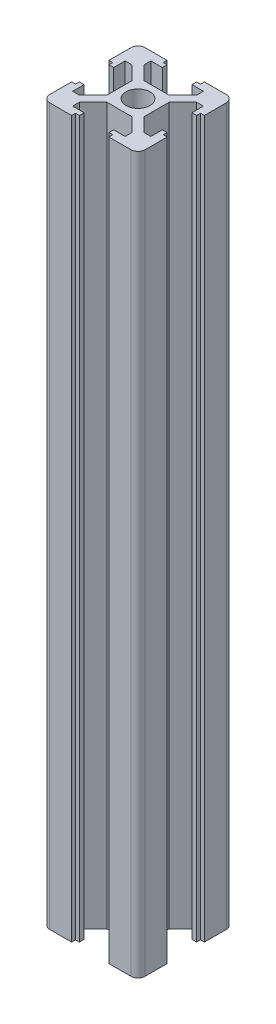
SolidWorks part; units mm, degrees
material "6063-O"
ref_plane "Front Plane" through (0, 0, 0) normal (0, 0, 1) x (1, 0, 0)
ref_plane "Top Plane" through (0, 0, 0) normal (0, 1, 0) x (1, 0, 0)
ref_plane "Right Plane" through (0, 0, 0) normal (1, 0, 0) x (0, 0, -1)
sketch "Sketch1" plane through (0, 0, 0) normal (0, 1, 0) x (1, 0, 0)
  line L0 (0, 14.5399) -> (0, 10) construction
  line L1 (-16.8658, 0) -> (2.5, 0) construction
  line L2 (13.2784, 3.9) -> (3.9, 3.9) construction
  line L3 (0, 0) -> (2.5, 0)
  line L4 (0, 0) -> (0, 2.5)
  line L5 (3.9, 10) -> (8.5, 10)
  line L6 (9.2, 0) -> (16.4291, 0) construction
  line L7 (-2.63, 3.9) -> (2.63, 3.9)
  line L9 (2.5491, 3.9) -> (2.63, 3.9)
  line L10 (3.9, 0) -> (3.9, 2.63)
  line L11 (13.2784, 3.1) -> (2.5491, 3.1) construction
  line L12 (8.2, 7.5573) -> (8.2, -3.0868) construction
  line L13 (9.2, 7.2593) -> (9.2, -8.1534) construction
  line L14 (10, 3.9) -> (9.2, 3.9)
  line L15 (9.2, 3.9) -> (9.2, 3.1)
  line L16 (9.2, 3.1) -> (8.2, 3.1)
  line L17 (8.2, 3.1) -> (8.2, 5.5)
  line L18 (8.2, 5.5) -> (6.77, 5.5)
  line L19 (6.77, 5.5) -> (3.9, 2.63)
  line L20 (5.0973, 5.5) -> (13.0082, 5.5) construction
  line L21 (3.1, 11.2046) -> (3.1, 2.6994) construction
  line L22 (3.9, 10.7498) -> (3.9, 3.9) construction
  line L23 (5.5, 11.523) -> (5.5, 1.4941) construction
  line L24 (-2.2597, 8.2) -> (6.1545, 8.2) construction
  line L25 (-2.9419, 9.2) -> (5.7225, 9.2) construction
  line L26 (3.9, 10) -> (3.9, 9.2)
  line L27 (3.9, 9.2) -> (3.1, 9.2)
  line L28 (3.1, 9.2) -> (3.1, 8.2)
  line L29 (3.1, 8.2) -> (5.5, 8.2)
  line L30 (5.5, 8.2) -> (5.5, 6.77)
  line L31 (5.5, 6.77) -> (2.63, 3.9)
  line L32 (0, 2.5) -> (0, -14.4122) construction
  line L33 (10, 3.9) -> (10, 8.5)
  line L34 (9.2, 0) -> (10, 0)
  line L35 (2.63, 3.9) -> (2.5491, 3.9) construction
  line L36 (3.9, 2.63) -> (3.9, 2.0627) construction
  line L37 (10, -3.9) -> (10, -8.5)
  line L38 (3.9, -10) -> (8.5, -10)
  line L39 (3.9, -10) -> (3.9, -9.2)
  line L40 (3.9, -9.2) -> (3.1, -9.2)
  line L41 (3.1, -9.2) -> (3.1, -8.2)
  line L42 (3.1, -8.2) -> (5.5, -8.2)
  line L43 (5.5, -8.2) -> (5.5, -6.77)
  line L44 (5.5, -6.77) -> (2.63, -3.9)
  line L45 (0, -3.9) -> (2.63, -3.9)
  line L46 (3.9, 0) -> (3.9, -2.63)
  line L47 (6.77, -5.5) -> (3.9, -2.63)
  line L48 (8.2, -5.5) -> (6.77, -5.5)
  line L49 (8.2, -3.1) -> (8.2, -5.5)
  line L50 (9.2, -3.1) -> (8.2, -3.1)
  line L51 (9.2, -3.9) -> (9.2, -3.1)
  line L52 (10, -3.9) -> (9.2, -3.9)
  line L53 (-3.9, -10) -> (-8.5, -10)
  line L54 (-10, -3.9) -> (-10, -8.5)
  line L55 (-10, -3.9) -> (-9.2, -3.9)
  line L56 (-9.2, -3.9) -> (-9.2, -3.1)
  line L57 (-9.2, -3.1) -> (-8.2, -3.1)
  line L58 (-8.2, -3.1) -> (-8.2, -5.5)
  line L59 (-8.2, -5.5) -> (-6.77, -5.5)
  line L60 (-6.77, -5.5) -> (-3.9, -2.63)
  line L61 (-3.9, 0) -> (-3.9, -2.63)
  line L62 (0, -3.9) -> (-2.63, -3.9)
  line L63 (-5.5, -6.77) -> (-2.63, -3.9)
  line L64 (-5.5, -8.2) -> (-5.5, -6.77)
  line L65 (-3.1, -8.2) -> (-5.5, -8.2)
  line L66 (-3.1, -9.2) -> (-3.1, -8.2)
  line L67 (-3.9, -9.2) -> (-3.1, -9.2)
  line L68 (-3.9, -10) -> (-3.9, -9.2)
  line L69 (-10, 3.9) -> (-10, 8.5)
  line L70 (-3.9, 10) -> (-8.5, 10)
  line L71 (-3.9, 10) -> (-3.9, 9.2)
  line L72 (-3.9, 9.2) -> (-3.1, 9.2)
  line L73 (-3.1, 9.2) -> (-3.1, 8.2)
  line L74 (-3.1, 8.2) -> (-5.5, 8.2)
  line L75 (-5.5, 8.2) -> (-5.5, 6.77)
  line L76 (-5.5, 6.77) -> (-2.63, 3.9)
  line L78 (-3.9, 0) -> (-3.9, 2.63)
  line L79 (-6.77, 5.5) -> (-3.9, 2.63)
  line L80 (-8.2, 5.5) -> (-6.77, 5.5)
  line L81 (-8.2, 3.1) -> (-8.2, 5.5)
  line L82 (-9.2, 3.1) -> (-8.2, 3.1)
  line L83 (-9.2, 3.9) -> (-9.2, 3.1)
  line L84 (-10, 3.9) -> (-9.2, 3.9)
  line L85 (0, 3.9) -> (-2.63, 3.9) [skipped]
  circle A0 centre (0, 0) radius 2.5
  arc A1 (8.5, 10) -> (10, 8.5) centre (8.5, 8.5) cw
  arc A2 (10, -8.5) -> (8.5, -10) centre (8.5, -8.5) cw
  arc A4 (-8.5, -10) -> (-10, -8.5) centre (-8.5, -8.5) cw
  arc A6 (-10, 8.5) -> (-8.5, 10) centre (-8.5, 8.5) cw
  point P12 (10, 10)
  point P126 (0, 0)
  dimension "D3" = 5
  dimension "D4" = 1.5
  dimension "D1" = 10
  dimension "D2" = 10
  dimension "D6" = 3.9
  dimension "D7" = 3.9
  dimension "D8" = 3.1
  dimension "D9" = 4
  dimension "D11" = 5.5
  dimension "D12" = 1.8
  dimension "D13" = 0.8
  dimension "D14" = 3.9
  dimension "D15" = 3.1
  dimension "D16" = 5.5
  dimension "D17" = 1.27
  dimension "D18" = 1.27
  dimension "D19" = 1.27
  dimension "D20" = 1.27
extrude "Boss-Extrude1" add sketch "Sketch1" along normal blind 150 contours A6 L69 L84 L83 L82 L81 L80 L79 L78 L61 L60 L59 L58 L57 L56 L55 L54 A4 L53 L68 L67 L66 L65 L64 L63 L62 L45 L44 L43 L42 L41 L40 L39 L38 A2 L37 L52 L51 L50 L49 L48 L47 L46 L10 L19 L18 L17 L16 L15 L14 L33 region at (6.2, 0, -9.7172)
